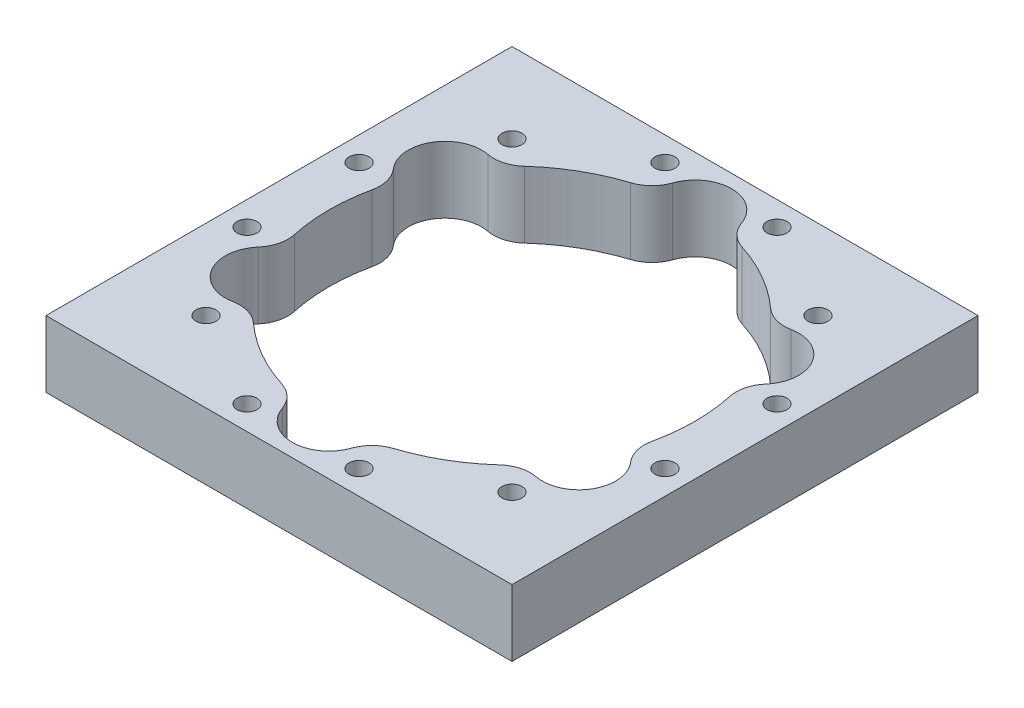
SolidWorks part; units mm, degrees
ref_plane "Front Plane" through (0, 0, 0) normal (0, 0, 1) x (1, 0, 0)
ref_plane "Top Plane" through (0, 0, 0) normal (0, 1, 0) x (1, 0, 0)
ref_plane "Right Plane" through (0, 0, 0) normal (1, 0, 0) x (0, 0, -1)
sketch "Sketch1" plane through (0, 0, 0) normal (0, 1, 0) x (1, 0, 0)
  line L0 (-49.1682, 0) -> (0, 0) construction
  line L1 (0, 0) -> (-48.4521, -12.9827) construction
  line L2 (-35, 35) -> (35, 35)
  line L3 (-35, 35) -> (-35, -35)
  line L4 (35, 35) -> (35, -35)
  line L5 (-35, -35) -> (35, -35)
  circle A0 centre (0, 0) radius 35 construction
  circle A1 centre (0, 0) radius 32.5 construction
  circle A2 centre (0, 0) radius 27.5
  circle A3 centre (0, 27.5) radius 5.5
  circle A4 centre (23.8157, 13.75) radius 5.5
  circle A5 centre (23.8157, -13.75) radius 5.5
  circle A6 centre (0, -27.5) radius 5.5
  circle A7 centre (-23.8157, -13.75) radius 5.5
  circle A8 centre (-23.8157, 13.75) radius 5.5
  circle A9 centre (-31.3926, -8.4116) radius 1.5
  circle A10 centre (-31.3926, 8.4116) radius 1.5
  circle A11 centre (-22.981, 22.981) radius 1.5
  circle A12 centre (-8.4116, 31.3926) radius 1.5
  circle A13 centre (8.4116, 31.3926) radius 1.5
  circle A14 centre (22.981, 22.981) radius 1.5
  circle A15 centre (31.3926, 8.4116) radius 1.5
  circle A16 centre (31.3926, -8.4116) radius 1.5
  circle A17 centre (22.981, -22.981) radius 1.5
  circle A18 centre (8.4116, -31.3926) radius 1.5
  circle A19 centre (-8.4116, -31.3926) radius 1.5
  circle A20 centre (-22.981, -22.981) radius 1.5
  point P19 (0, 0)
  point P47 (0, 0)
  dimension "D1" = 70
  dimension "D2" = 65
  dimension "D3" = 55
  dimension "D4" = 11
  dimension "D7" = 3
  dimension "D6" = 15
  dimension "D5" = 6
  dimension "D8" = 12
extrude "Boss-Extrude1" add sketch "Sketch1" along normal blind 10 contours A0 A20 A19 A18 A17 A16 A15 A14 A13 A12 A11 A10 A9 A8 A2 A3 A4 A5 A6 A7 region at (0, 0, -34.0101)
fillet "Fillet1" radius 5 12 edges at (5.4724, 5, -26.95) (20.6032, 5, -18.2143) (26.0756, 5, 8.7357) (26.0756, 5, -8.7357) (20.6032, 5, 18.2143) (5.4724, 5, 26.95) (-5.4724, 5, 26.95) (-20.6032, 5, 18.2143) (-26.0756, 5, 8.7357) (-26.0756, 5, -8.7357) (-20.6032, 5, -18.2143) (-5.4724, 5, -26.95)
